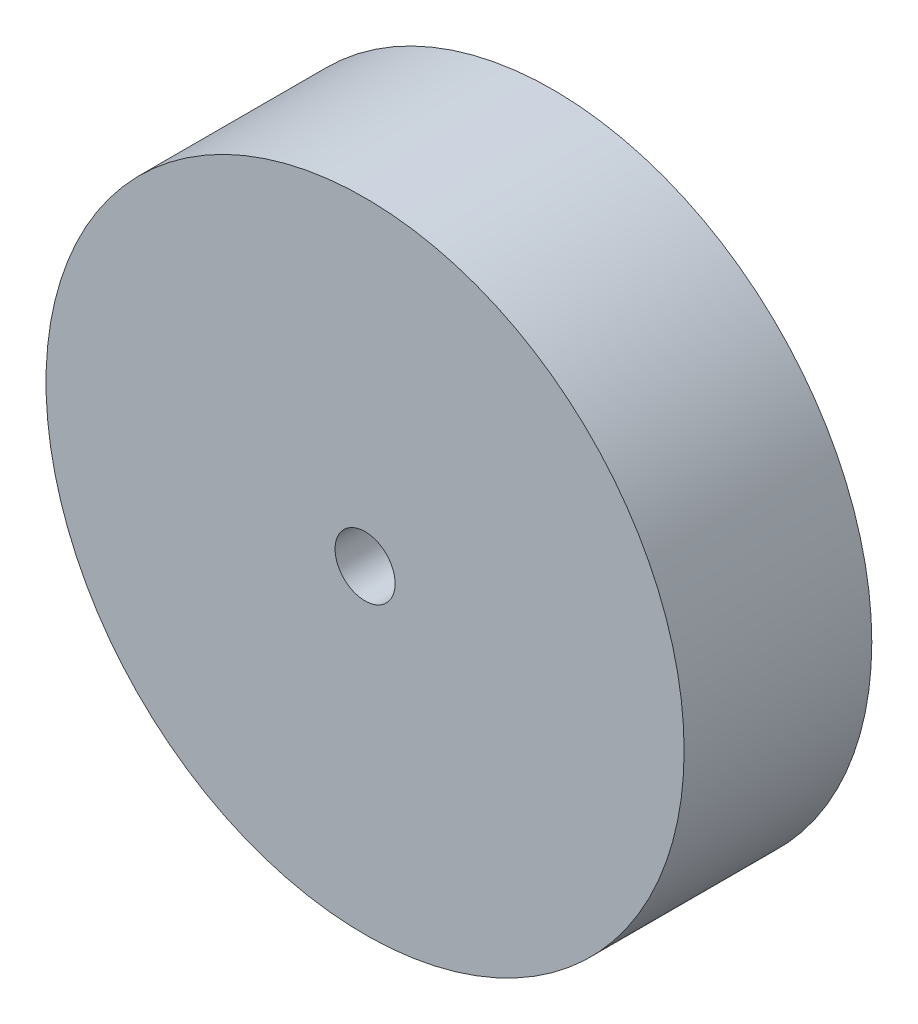
SolidWorks part; units mm, degrees
ref_plane "Front Plane" through (0, 0, 0) normal (0, 0, 1) x (1, 0, 0)
ref_plane "Top Plane" through (0, 0, 0) normal (0, 1, 0) x (1, 0, 0)
ref_plane "Right Plane" through (0, 0, 0) normal (1, 0, 0) x (0, 0, -1)
sketch "Sketch1" plane through (0, 0, 0) normal (0, 0, 1) x (1, 0, 0)
  circle A0 centre (0, 0) radius 17
  circle A1 centre (0, 0) radius 1.6
  dimension "D1" = 34
  dimension "D2" = 3.2
extrude "Boss-Extrude1" add sketch "Sketch1" along normal blind 10
